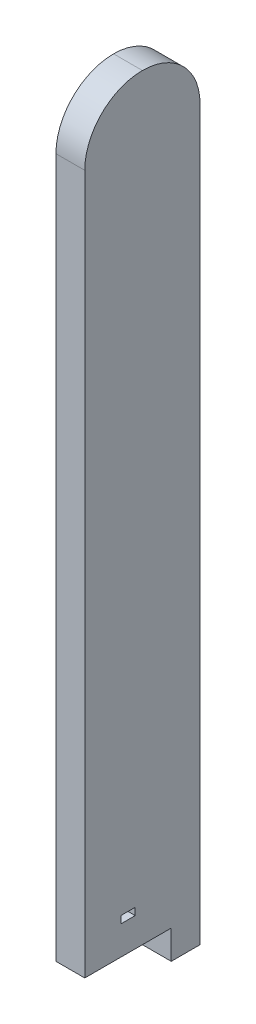
SolidWorks part; units mm, degrees
ref_plane "Front Plane" through (0, 0, 0) normal (0, 0, 1) x (1, 0, 0)
ref_plane "Top Plane" through (0, 0, 0) normal (0, 1, 0) x (1, 0, 0)
ref_plane "Right Plane" through (0, 0, 0) normal (1, 0, 0) x (0, 0, -1)
sketch "Sketch1" plane through (0, 0, 0) normal (1, 0, 0) x (0, 0, -1)
  line L0 (12.7, -69.5376) -> (12.7, -160.4412)
  line L1 (-12.7, 12.7) -> (12.7, 12.7)
  line L2 (-12.7, 12.7) -> (-12.7, -154.0912)
  line L3 (-12.7, -154.0912) -> (6.35, -154.0912)
  line L4 (12.7, 12.7) -> (12.7, -69.5376)
  line L5 (226.2399, -72.5457) -> (-123.236, -225.7259) construction
  line L7 (12.7, -160.4412) -> (6.35, -160.4412)
  line L8 (6.35, -160.4412) -> (6.35, -154.0912)
  line L9 (4.503, -157.2662) -> (-49995.497, -157.2662) construction
  line L11 (-12.7, 12.7) -> (0, 0) construction
  line L12 (0, 0) -> (12.7, 12.7) construction
  circle A0 centre (0, 0) radius 157.2662 construction
  point P0 (0, 0)
  point P11 (6.35, -157.2662)
  dimension "D1" = 25.4
  dimension "D2" = 6.35
  dimension "D3" = 6.35
extrude "Boss-Extrude1" add sketch "Sketch1" along normal mid plane 6.35
fillet "Fillet1" radius 12.7 2 edges at (0, 12.7, -12.7) (0, 12.7, 12.7)
sketch "Sketch2" plane through (3.175, 0, 0) normal (1, 0, 0) x (0, 0, -1)
  line L1 (-4.7625, -147.7412) -> (-1.5875, -147.7412)
  line L2 (-4.7625, -147.7412) -> (-4.7625, -146.1537)
  line L3 (-4.7625, -146.1537) -> (-1.5875, -146.1537)
  line L4 (-1.5875, -147.7412) -> (-1.5875, -146.1537)
  line L5 (-4.7625, -147.7412) -> (-1.5875, -146.1537) construction
  line L6 (-4.7625, -146.1537) -> (-1.5875, -147.7412) construction
  line L7 (-3.175, -154.0912) -> (-3.175, -146.9474) construction
  line L8 (-12.7, -154.0912) -> (6.35, -154.0912) construction
  point P0 (-3.175, -146.9474)
  dimension "D1" = 6.35
  dimension "D2" = 1.5875
  dimension "D3" = 3.175
extrude "Cable-tie hole" cut sketch "Sketch2" against normal through all
